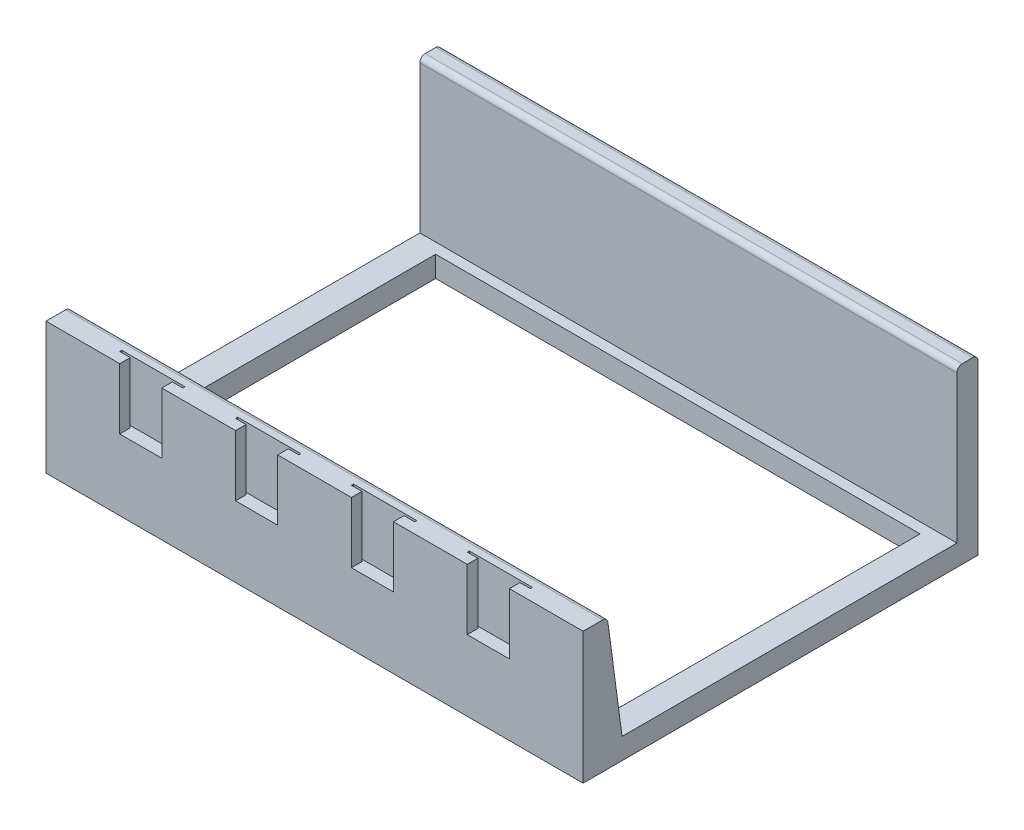
SolidWorks part; units mm, degrees
ref_plane "前视基准面" through (0, 0, 0) normal (0, 0, 1) x (1, 0, 0)
ref_plane "上视基准面" through (0, 0, 0) normal (0, 1, 0) x (1, 0, 0)
ref_plane "右视基准面" through (0, 0, 0) normal (1, 0, 0) x (0, 0, -1)
other "Configuration Table"
sketch "草图1" plane through (0, 0, 0) normal (0, 1, 0) x (1, 0, 0)
  line L1 (0, 0) -> (-102, 0)
  line L2 (0, 0) -> (0, 75)
  line L3 (0, 75) -> (-102, 75)
  line L4 (-102, 0) -> (-102, 75)
  dimension "D1" = 102
  dimension "D2" = 75
extrude "凸台-拉伸1" add sketch "草图1" along normal blind 25
sketch "草图2" plane through (0, 25, 0) normal (0, 1, 0) x (1, 0, 0)
  line L0 (-102, 75) -> (-102, 0) construction
  line L1 (-90, 2) -> (-88, 2)
  line L2 (-90, 2) -> (-90, 2.4)
  line L3 (-90, 2.4) -> (-78, 2.4)
  line L4 (-78, 2) -> (-78, 2.4)
  line L5 (-68, 2) -> (-66, 2)
  line L6 (-68, 2) -> (-68, 2.4)
  line L7 (-68, 2.4) -> (-56, 2.4)
  line L8 (-56, 2) -> (-56, 2.4)
  line L9 (-46, 2.4) -> (-34, 2.4)
  line L10 (-46, 2.4) -> (-46, 2)
  line L11 (-46, 2) -> (-44, 2)
  line L12 (-34, 2.4) -> (-34, 2)
  line L13 (-24, 2.4) -> (-12, 2.4)
  line L14 (-24, 2.4) -> (-24, 2)
  line L15 (-24, 2) -> (-22, 2)
  line L16 (-12, 2.4) -> (-12, 2)
  line L19 (-102, 0) -> (0, 0) construction
  line L20 (-14, 2) -> (-12, 2)
  line L22 (-88, 2) -> (-88, 0)
  line L23 (-88, 0) -> (-80, 0)
  line L24 (-80, 2) -> (-80, 0)
  line L26 (-66, 2) -> (-66, 0)
  line L27 (-66, 0) -> (-58, 0)
  line L28 (-58, 2) -> (-58, 0)
  line L30 (-44, 2) -> (-44, 0)
  line L31 (-44, 0) -> (-36, 0)
  line L32 (-36, 2) -> (-36, 0)
  line L34 (-22, 2) -> (-22, 0)
  line L35 (-22, 0) -> (-14, 0)
  line L36 (-14, 2) -> (-14, 0)
  line L37 (-36, 2) -> (-34, 2)
  line L38 (-58, 2) -> (-56, 2)
  line L39 (-80, 2) -> (-78, 2)
  point P16 (-68, 2.2)
  dimension "D1" = 12
  dimension "D2" = 12
  dimension "D3" = 12
  dimension "D4" = 12
  dimension "D5" = 10
  dimension "D6" = 10
  dimension "D7" = 10
  dimension "D8" = 12
  dimension "D9" = 2
  dimension "D10" = 2
  dimension "D11" = 2
  dimension "D12" = 2
  dimension "D13" = 0.4
  dimension "D14" = 0.4
  dimension "D15" = 0.4
  dimension "D16" = 0.4
  dimension "D17" = 2
  dimension "D18" = 2
  dimension "D19" = 2
  dimension "D20" = 2
  dimension "D21" = 2
  dimension "D22" = 2
  dimension "D23" = 2
  dimension "D24" = 2
extrude "切除-拉伸1" cut sketch "草图2" against normal offset from surface (11.56 mm away) 13.44 up to face at (-51, 0, -37.5)
sketch "草图3" plane through (0, 25, 0) normal (0, 1, 0) x (1, 0, 0)
  line L0 (0, 0) -> (0, 75) construction
  line L1 (-102, 75) -> (0, 75)
  line L2 (-102, 75) -> (-102, 7.4)
  line L3 (-102, 7.4) -> (0, 7.4)
  line L4 (0, 75) -> (0, 7.4)
  line L5 (-12, 2.4) -> (-24, 2.4) construction
  dimension "D1" = 5
extrude "切除-拉伸2" cut sketch "草图3" against normal blind 12
sketch "草图4" plane through (-102, 0, 0) normal (-1, 0, 0) x (0, 0, 1)
  line L6 (-75, 13) -> (-7.4, 13) construction
  line L7 (-71, 13) -> (-7.4, 13)
  line L8 (-71, 13) -> (-71, 4)
  line L9 (-71, 4) -> (-7.4, 4)
  line L10 (-7.4, 13) -> (-7.4, 4)
  line L11 (-75, 13) -> (-75, 0) construction
  line L12 (-75, 0) -> (0, 0) construction
  line L13 (-7.4, 13) -> (-7.4, 25) construction
  dimension "D1" = 4
  dimension "D2" = 4
extrude "切除-拉伸3" cut sketch "草图4" against normal through all
sketch "草图6" plane through (0, 13, 0) normal (0, 1, 0) x (1, 0, 0)
  line L4 (-102, 71) -> (0, 71)
  line L5 (0, 71) -> (0, 75)
  line L6 (0, 75) -> (-102, 75)
  line L7 (-102, 75) -> (-102, 71)
  line L8 (-102, 71) -> (0, 71)
  line L9 (0, 71) -> (0, 75)
  line L10 (0, 75) -> (-102, 75)
  line L11 (-102, 75) -> (-102, 71)
  dimension "D1" = 0
extrude "凸台-拉伸2" add sketch "草图6" along normal blind 20
sketch "草图7" plane through (0, 4, 0) normal (0, 1, 0) x (1, 0, 0)
  line L0 (0, 71) -> (0, 7.4) construction
  line L1 (-97, 69) -> (-5, 69)
  line L2 (-97, 69) -> (-97, 9.4)
  line L3 (-97, 9.4) -> (-5, 9.4)
  line L4 (-5, 69) -> (-5, 9.4)
  line L5 (-102, 71) -> (-102, 7.4) construction
  line L6 (-102, 71) -> (0, 71) construction
  line L7 (0, 7.4) -> (-102, 7.4) construction
  dimension "D1" = 5
  dimension "D2" = 5
  dimension "D3" = 2
  dimension "D4" = 2
extrude "切除-拉伸5" cut sketch "草图7" against normal blind 8
sketch "草图9" plane through (-102, 0, 0) normal (-1, 0, 0) x (0, 0, 1)
  line L0 (-7.4, 25) -> (-4.6, 25)
  line L2 (-4.6, 25) -> (-7.4, 4)
  line L3 (-7.4, 4) -> (-7.4, 25)
  dimension "D1" = 2.8
extrude "切除-拉伸6" cut sketch "草图9" against normal blind 108
fillet "圆角2" radius 1 3 edges at (-51, 33, -75) (-51, 33, -71) (-51, 25, -4.6)
